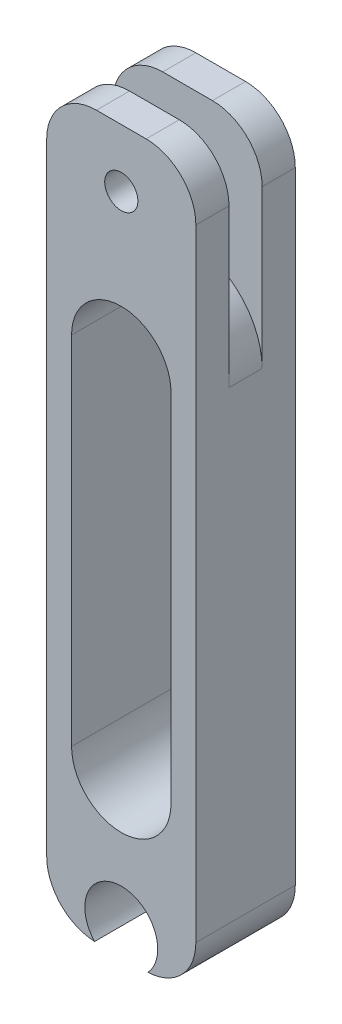
SolidWorks part; units mm, degrees
ref_plane "Alzado" through (0, 0, 0) normal (0, 0, 1) x (1, 0, 0)
ref_plane "Planta" through (0, 0, 0) normal (0, 1, 0) x (1, 0, 0)
ref_plane "Vista lateral" through (0, 0, 0) normal (1, 0, 0) x (0, 0, -1)
sketch "Croquis1" plane through (0, 0, 0) normal (0, 0, 1) x (1, 0, 0)
  line L0 (0, 0) -> (0, 42) construction
  line L1 (-4.5, -1.5) -> (-1.6093, -1.5)
  line L2 (-4.5, -1.5) -> (-4.5, 42)
  line L3 (-4.5, 42) -> (4.5, 42)
  line L4 (4.5, -1.5) -> (4.5, 42)
  line L5 (-4.5017, -2.2) -> (4.5216, -2.2) construction
  line L6 (1.6093, -1.5) -> (4.5, -1.5)
  circle A0 centre (0, 0) radius 2.2 construction
  circle A1 centre (0, 38.5) radius 1
  arc A2 (-1.6093, -1.5) -> (1.6093, -1.5) centre (0, 0) cw
  dimension "D1" = 4.4
  dimension "D3" = 2
  dimension "D2" = 0.7
  dimension "D4" = 38.5
  dimension "D5" = 3.5
  dimension "D6" = 9
extrude "Saliente-Extruir1" add sketch "Croquis1" along normal blind 6
sketch "Croquis2" plane through (0, 42, 0) normal (0, 1, 0) x (1, 0, 0)
  line L0 (-4.5, -3) -> (4.5, -3) construction
  line L1 (-4.5, -6) -> (-4.5, 0) construction
  line L2 (4.5, -6) -> (4.5, 0) construction
  line L4 (-4.5, -2) -> (4.5, -2)
  line L5 (-4.5, -2) -> (-4.5, -4)
  line L6 (-4.5, -4) -> (4.5, -4)
  line L7 (4.5, -2) -> (4.5, -4)
  dimension "D1" = 2
extrude "Cortar-Extruir1" cut sketch "Croquis2" against normal blind 8
fillet "Redondeo1" radius 4.5 2 edges at (-4.5, 34, 3) (4.5, 34, 3)
fillet "Redondeo2" radius 3 6 edges at (-4.5, 42, 5) (-4.5, 42, 1) (4.5, 42, 1) (4.5, 42, 5) (4.5, -1.5, 3) (-4.5, -1.5, 3)
sketch "Croquis3" plane through (0, 0, 6) normal (0, 0, 1) x (1, 0, 0)
  line L0 (0, 38.5) -> (0, 0) construction
  line L1 (0, 8) -> (0, 29.5) construction
  line L2 (-3, 8) -> (-3, 29.5)
  line L3 (3, 8) -> (3, 29.5)
  arc A0 (-3, 8) -> (3, 8) centre (0, 8) ccw
  arc A1 (3, 29.5) -> (-3, 29.5) centre (0, 29.5) ccw
  arc A2 (4.5, 29.5) -> (0, 34) centre (0, 29.5) ccw construction
  point P6 (0, 18.75)
  dimension "D1" = 3
  dimension "D2" = 8
extrude "Cortar-Extruir2" cut sketch "Croquis3" against normal through all
move or copy body "Sólido-Mover/Copiar1" [suppressed] bodies to move or copy 103 placed by mates yes
